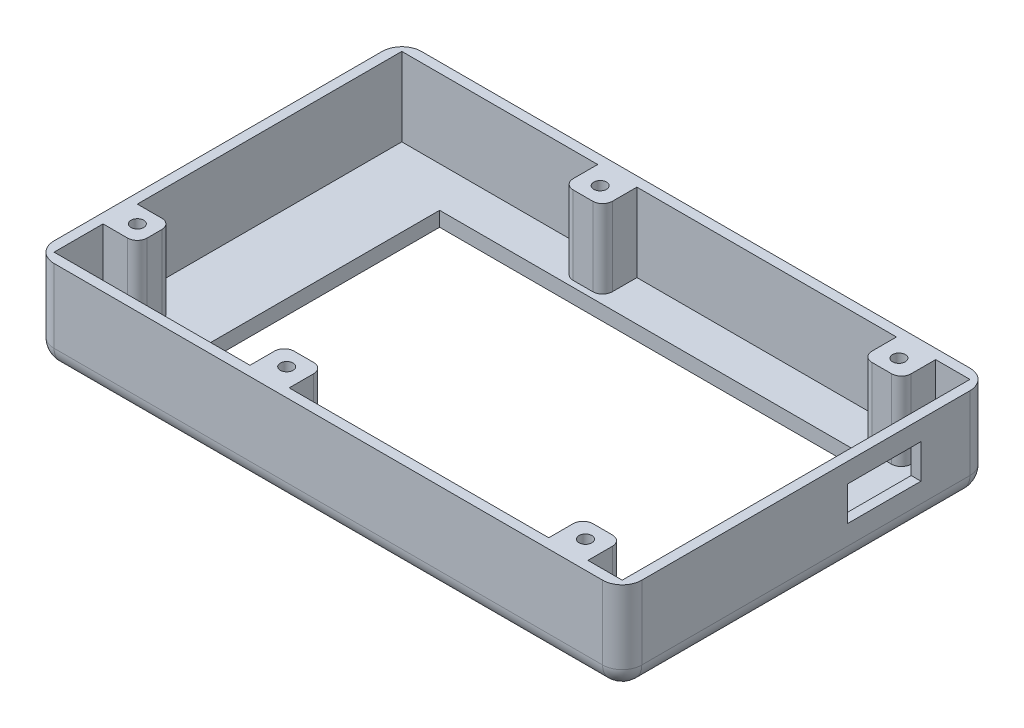
SolidWorks part; units mm, degrees
ref_plane "Front Plane" through (0, 0, 0) normal (0, 0, 1) x (1, 0, 0)
ref_plane "Top Plane" through (0, 0, 0) normal (0, 1, 0) x (1, 0, 0)
ref_plane "Right Plane" through (0, 0, 0) normal (1, 0, 0) x (0, 0, -1)
sketch "Sketch1" plane through (0, 0, 0) normal (0, 1, 0) x (1, 0, 0)
  line L1 (-60, 37.5) -> (60, 37.5)
  line L2 (-60, 37.5) -> (-60, -37.5)
  line L3 (-60, -37.5) -> (60, -37.5)
  line L4 (60, 37.5) -> (60, -37.5)
  line L5 (-60, 37.5) -> (60, -37.5) construction
  line L6 (-60, -37.5) -> (60, 37.5) construction
  point P0 (0, 0)
  dimension "D1" = 120
  dimension "D2" = 75
extrude "Boss-Extrude1" add sketch "Sketch1" along normal blind 19
sketch "Sketch2" plane through (0, 19, 0) normal (0, 1, 0) x (1, 0, 0)
  line L1 (-58, 35.5) -> (58, 35.5)
  line L2 (-58, 35.5) -> (-58, -35.5)
  line L3 (-58, -35.5) -> (58, -35.5)
  line L4 (58, 35.5) -> (58, -35.5)
  line L5 (-58, 35.5) -> (58, -35.5) construction
  line L6 (-58, -35.5) -> (58, 35.5) construction
  point P0 (0, 0)
  dimension "D1" = 71
  dimension "D2" = 116
extrude "Cut-Extrude1" cut sketch "Sketch2" against normal blind 16
fillet "Fillet1" radius 4 8 edges at (-60, 9.5, -37.5) (-60, 9.5, 37.5) (-60, 0, 0) (60, 9.5, -37.5) (0, 0, -37.5) (60, 0, 0) (0, 0, 37.5) (60, 9.5, 37.5)
sketch "Sketch5" plane through (0, 0, 0) normal (0, -1, 0) x (1, 0, 0)
  line L0 (56, 33.5) -> (-56, 33.5) construction
  line L1 (-42.04, 27.7) -> (42.95, 27.7)
  line L2 (-42.04, 27.7) -> (-42.04, -27.26)
  line L3 (-42.04, -27.26) -> (42.95, -27.26)
  line L4 (42.95, 27.7) -> (42.95, -27.26)
  line L5 (-42.04, 27.7) -> (42.95, -27.26) construction
  line L6 (-42.04, -27.26) -> (42.95, 27.7) construction
  line L7 (-56, -33.5) -> (56, -33.5) construction
  line L8 (-56, 33.5) -> (-56, -33.5) construction
  line L9 (56, -33.5) -> (56, 33.5) construction
  point P0 (0.455, 0.22)
  dimension "D1" = 5.8
  dimension "D2" = 6.24
  dimension "D3" = 13.96
  dimension "D4" = 13.05
extrude "Cut-Extrude2" cut sketch "Sketch5" against normal blind 3
sketch "Sketch6" plane through (0, 3, 0) normal (0, 1, 0) x (1, 0, 0)
  line L0 (-58, 35.5) -> (-58, -35.5) construction
  line L1 (43, -28.5) -> (51, -28.5)
  line L2 (43, -28.5) -> (43, -35.5)
  line L3 (43, -35.5) -> (51, -35.5)
  line L4 (51, -28.5) -> (51, -35.5)
  line L5 (43, -28.5) -> (51, -35.5) construction
  line L6 (43, -35.5) -> (51, -28.5) construction
  line L7 (43, 35.5) -> (51, 35.5)
  line L8 (43, 35.5) -> (43, 28.5)
  line L9 (43, 28.5) -> (51, 28.5)
  line L10 (51, 35.5) -> (51, 28.5)
  line L11 (43, 35.5) -> (51, 28.5) construction
  line L12 (43, 28.5) -> (51, 35.5) construction
  line L13 (58, 35.5) -> (-58, 35.5) construction
  line L14 (-58, -35.5) -> (58, -35.5) construction
  line L15 (58, -35.5) -> (58, 35.5) construction
  line L16 (-18, 35.5) -> (-10, 35.5)
  line L17 (-18, 35.5) -> (-18, 28.5)
  line L18 (-18, 28.5) -> (-10, 28.5)
  line L19 (-10, 35.5) -> (-10, 28.5)
  line L20 (-18, 35.5) -> (-10, 28.5) construction
  line L21 (-18, 28.5) -> (-10, 35.5) construction
  line L22 (-18, -28.5) -> (-10, -28.5)
  line L23 (-18, -28.5) -> (-18, -35.5)
  line L24 (-18, -35.5) -> (-10, -35.5)
  line L25 (-10, -28.5) -> (-10, -35.5)
  line L26 (-18, -28.5) -> (-10, -35.5) construction
  line L27 (-18, -35.5) -> (-10, -28.5) construction
  line L28 (58, -35.5) -> (58, 35.5) construction
  line L29 (-58, -18.5) -> (-51, -18.5)
  line L30 (-58, -18.5) -> (-58, -25.5)
  line L31 (-58, -25.5) -> (-51, -25.5)
  line L32 (-51, -18.5) -> (-51, -25.5)
  line L33 (-58, -18.5) -> (-51, -25.5) construction
  line L34 (-58, -25.5) -> (-51, -18.5) construction
  point P0 (47, -32)
  point P5 (47, 32)
  point P16 (-14, 32)
  point P21 (-14, -32)
  point P28 (-54.5, -22)
  dimension "D1" = 8
  dimension "D2" = 8
  dimension "D3" = 7
  dimension "D4" = 7
  dimension "D5" = 7
  dimension "D6" = 7
  dimension "D7" = 0
  dimension "D8" = 0
  dimension "D9" = 8
  dimension "D10" = 8
  dimension "D11" = 7
  dimension "D12" = 7
  dimension "D13" = 0
  dimension "D14" = 0
  dimension "D15" = 40
  dimension "D16" = 40
  dimension "D17" = 7
  dimension "D18" = 7
  dimension "D19" = 10
  dimension "D20" = 0
extrude "Boss-Extrude2" add sketch "Sketch6" along normal blind 16
sketch "Sketch7" plane through (0, 19, 0) normal (0, 1, 0) x (1, 0, 0)
  line L0 (43, 35.5) -> (43, 28.5) construction
  line L1 (43, 28.5) -> (51, 28.5) construction
  line L2 (43, -28.5) -> (43, -35.5) construction
  line L4 (51, -28.5) -> (43, -28.5) construction
  line L5 (-18, 28.5) -> (-10, 28.5) construction
  line L6 (-18, 35.5) -> (-18, 28.5) construction
  line L7 (-18, -28.5) -> (-18, -35.5) construction
  line L8 (-10, -28.5) -> (-18, -28.5) construction
  line L11 (-51, -18.5) -> (-58, -18.5) construction
  line L12 (-51, -25.5) -> (-51, -18.5) construction
  circle A0 centre (47, 32) radius 1.3
  circle A1 centre (47, -32) radius 1.3
  circle A2 centre (-14, 32) radius 1.3
  circle A3 centre (-14, -32) radius 1.3
  circle A4 centre (-54.5, -22) radius 1.3
  dimension "D1" = 2.6
  dimension "D3" = 3.5
  dimension "D4" = 2.6
  dimension "D5" = 2.6
  dimension "D8" = 3.5
  dimension "D10" = 2.6
  dimension "D13" = 2.6
  dimension "D2" = 4
  dimension "D6" = 4
  dimension "D7" = 3.5
  dimension "D9" = 4
  dimension "D11" = 4
  dimension "D12" = 3.5
  dimension "D14" = 3.5
  dimension "D15" = 3.5
extrude "Cut-Extrude3" cut sketch "Sketch7" against normal blind 10
fillet "Fillet2" radius 2 10 edges at (-18, 11, 28.5) (-10, 11, 28.5) (43, 11, 28.5) (51, 11, 28.5) (43, 11, -28.5) (51, 11, -28.5) (-10, 11, -28.5) (-18, 11, -28.5) (-51, 11, 18.5) (-51, 11, 25.5)
sketch "Sketch8" plane through (60, 0, 0) normal (1, 0, 0) x (0, 0, -1)
  line L0 (-33.5, 4) -> (33.5, 4) construction
  line L1 (8.5, 15) -> (23.5, 15)
  line L2 (8.5, 15) -> (8.5, 8)
  line L3 (8.5, 8) -> (23.5, 8)
  line L4 (23.5, 15) -> (23.5, 8)
  line L5 (8.5, 15) -> (23.5, 8) construction
  line L6 (8.5, 8) -> (23.5, 15) construction
  line L7 (33.5, 4) -> (33.5, 19) construction
  point P0 (16, 11.5)
  dimension "D1" = 7
  dimension "D2" = 15
  dimension "D3" = 4
  dimension "D4" = 10
extrude "Cut-Extrude4" cut sketch "Sketch8" against normal blind 10
